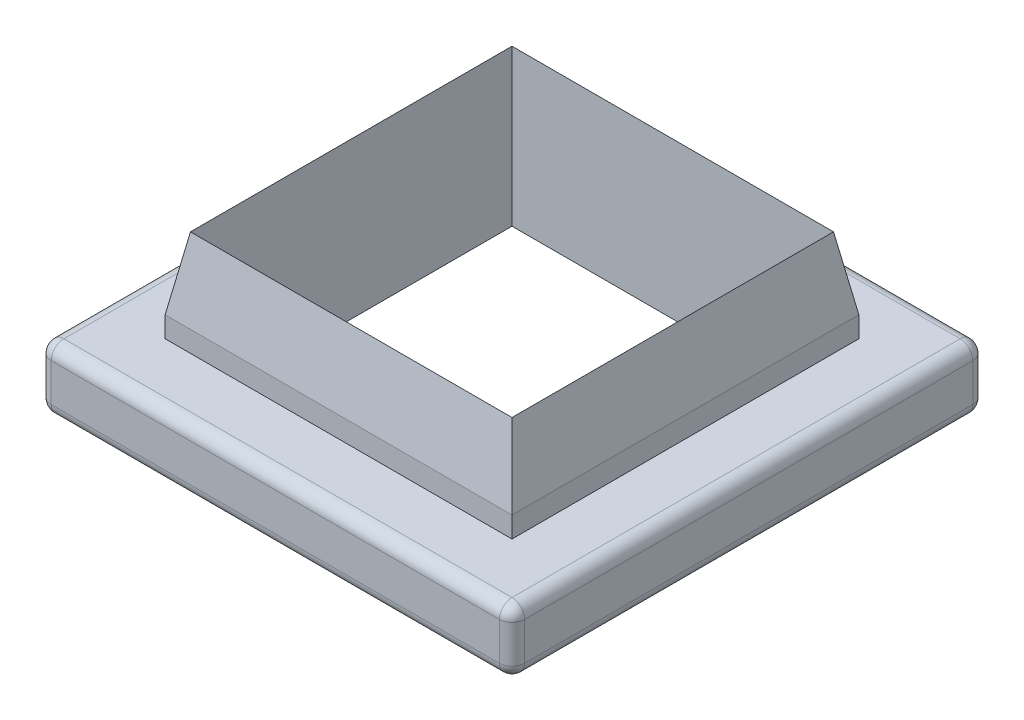
SolidWorks part; units mm, degrees
ref_plane "Front Plane" through (0, 0, 0) normal (0, 0, 1) x (1, 0, 0)
ref_plane "Top Plane" through (0, 0, 0) normal (0, 1, 0) x (1, 0, 0)
ref_plane "Right Plane" through (0, 0, 0) normal (1, 0, 0) x (0, 0, -1)
sketch "Sketch1" plane through (0, 0, 0) normal (0, 1, 0) x (1, 0, 0)
  line L12 (-5, -5) -> (-5, 32.4)
  line L13 (0, 0) -> (27.4, 0)
  line L14 (0, 0) -> (0, 27.4)
  line L15 (0, 27.4) -> (27.4, 27.4)
  line L16 (27.4, 0) -> (27.4, 27.4)
  line L17 (-5, 32.4) -> (32.4, 32.4)
  line L18 (32.4, -5) -> (32.4, 32.4)
  line L19 (-5, -5) -> (32.4, -5)
  line L20 (1, 1) -> (1, 26.4)
  line L21 (1, 26.4) -> (26.4, 26.4)
  line L22 (26.4, 1) -> (26.4, 26.4)
  line L23 (1, 1) -> (26.4, 1)
  dimension "D1" = 27.4
  dimension "D2" = 27.4
  dimension "D3" = 5
  dimension "D4" = 1
extrude "Boss-Extrude1" add sketch "Sketch1" along normal blind 35 contours L13 L16 L15 L14 L23 L20 L21 L22 region at (0.3875, 0, -13.7)
extrude "Boss-Extrude2" add sketch "Sketch1<3>" along normal blind 5 contours L12 L19 L18 L17 L16 L13 L14 L15 region at (-4.4711, 0, -13.7)
sketch "Sketch1<3>" plane through (0, 0, 0) normal (0, 1, 0) x (1, 0, 0) same geometry as "Sketch1"
chamfer "Chamfer1" distance 5 angle 80 4 edges at (13.7, 35, -27.4) (27.4, 35, -13.7) (13.7, 35, 0) (0, 35, -13.7) first distance on face at (13.7, 35, -13.7)
fillet "Fillet1" radius 1 12 edges at (-5, 2.5, 5) (13.7, 5, 5) (32.4, 2.5, 5) (13.7, 0, 5) (13.7, 0, -32.4) (13.7, 5, -32.4) (32.4, 2.5, -32.4) (32.4, 0, -13.7) (32.4, 5, -13.7) (-5, 2.5, -32.4) (-5, 5, -13.7) (-5, 0, -13.7)
